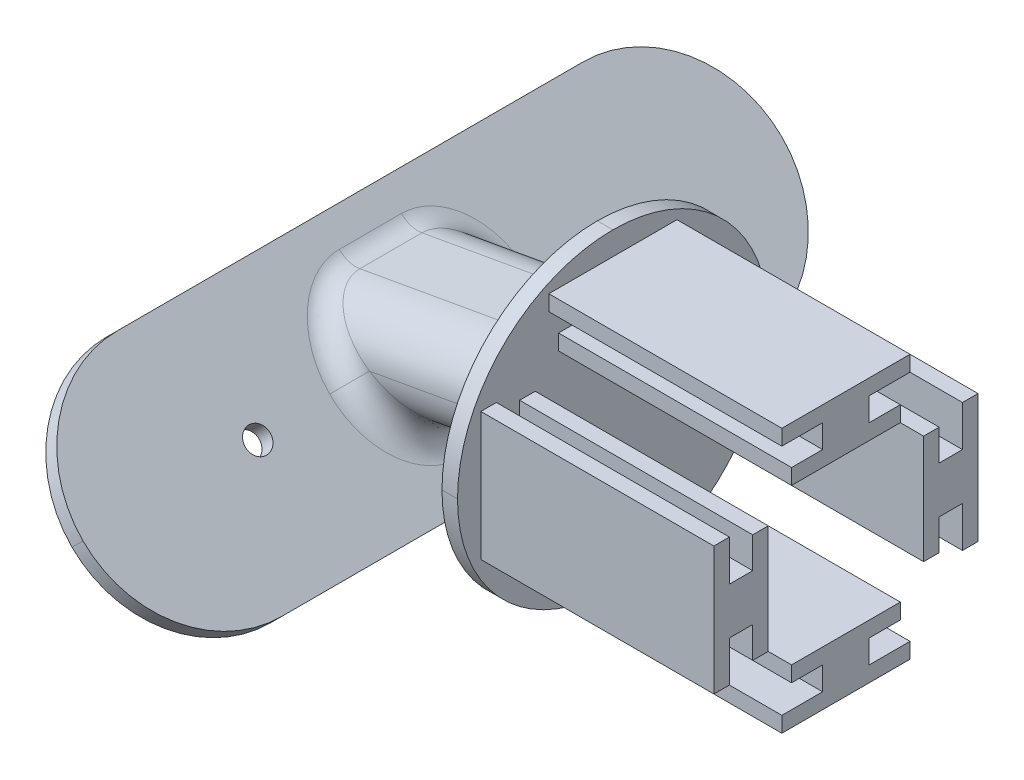
SolidWorks part; units mm, degrees
ref_plane "Front Plane" through (0, 0, 0) normal (0, 0, 1) x (1, 0, 0)
ref_plane "Top Plane" through (0, 0, 0) normal (0, 1, 0) x (1, 0, 0)
ref_plane "Right Plane" through (0, 0, 0) normal (1, 0, 0) x (0, 0, -1)
sketch "Sketch1" plane through (0, 0, 0) normal (0, 0, 1) x (1, 0, 0)
  line L0 (0, -20) -> (0, 20)
  line L1 (0, -20) -> (0, -25) construction
  line L2 (0, -25) -> (-10.6066, -14.3934) construction
  line L3 (-10.6066, -14.3934) -> (-31.8198, 6.8198)
  line L4 (-31.8198, 6.8198) -> (-33.234, 5.4056)
  line L5 (-33.234, 5.4056) -> (-12.0208, -15.8076)
  line L6 (-12.0208, -15.8076) -> (-10.6066, -14.3934)
  line L7 (0, 20) -> (2, 20)
  line L8 (2, 20) -> (2, -20)
  line L9 (0, -20) -> (2, -20)
  line L10 (-21.2132, -3.7868) -> (0, 0)
  line L11 (-28.1087, 3.1087) -> (0, 8.1265)
  line L12 (-20.5103, -7.7245) -> (-20.1654, -7.663)
  line L13 (-17.7654, -7.2346) -> (0, -4.0632)
  line L14 (-28.1087, 3.1087) -> (-21.2132, -3.7868)
  line L15 (-20.5103, -7.7245) -> (0.7029, -3.9378) construction
  line L16 (-21.2132, -3.7868) -> (-17.7654, -7.2346)
  line L17 (0, 8.1265) -> (0, 0)
  line L18 (0, -4.0632) -> (0, 0)
  point P4 (0, 0)
  dimension "D1" = 40
  dimension "D2" = 5
  dimension "D3" = 45
  dimension "D4" = 15
  dimension "D5" = 30
  dimension "D6" = 2
  dimension "D7" = 2
  dimension "D8" = 8
  dimension "D9" = 4
extrude "Boss-Extrude1" add sketch "Sketch1" along normal mid plane 90 contours L5 L6 L3 L4 region at (-21.9203, -4.4939, 0)
extrude "Boss-Extrude2" add sketch "Sketch1<3>" along normal mid plane 40 separate body contours L0 L7 L8 L9
sketch "Sketch1<3>" plane through (0, 0, 0) normal (0, 0, 1) x (1, 0, 0) same geometry as "Sketch1"
extrude "Boss-Extrude3" add sketch "Sketch1<4>" along normal mid plane 20 contours L11 L3 L10 L0 | L3 L13 L0 L10 region at (-9.7701, -3.7158, 0) region at (-12.4108, 2.0371, 0)
sketch "Sketch1<4>" plane through (0, 0, 0) normal (0, 0, 1) x (1, 0, 0) same geometry as "Sketch1"
sketch "Sketch2" plane through (2, 0, 0) normal (1, 0, 0) x (0, 0, -1)
  line L0 (0, 0) -> (0, 20) construction
  line L1 (-20, 20) -> (20, 20) construction
  line L2 (0, 0) -> (0, 15) construction
  line L3 (-15, -15) -> (15, -15) construction
  line L4 (-15, -15) -> (-15, 15) construction
  line L5 (-15, 15) -> (15, 15) construction
  line L6 (15, -15) -> (15, 15) construction
  line L7 (-15, -15) -> (15, 15) construction
  line L8 (-15, 15) -> (15, -15) construction
  line L9 (-8.25, 15) -> (8.25, 15)
  line L10 (-8.25, 15) -> (-8.25, 17)
  line L11 (-8.25, 17) -> (8.25, 17)
  line L12 (8.25, 17) -> (8.25, 15)
  line L13 (-7, 12) -> (7, 12)
  line L14 (-7, 12) -> (-7, 10)
  line L15 (-7, 10) -> (7, 10)
  line L16 (7, 10) -> (7, 12)
  line L17 (-3, 15) -> (-3, 12)
  line L18 (3, 15) -> (3, 12)
  line L19 (15, 8.25) -> (15, -8.25)
  line L20 (17, -8.25) -> (15, -8.25)
  line L21 (17, 8.25) -> (17, -8.25)
  line L22 (15, 8.25) -> (17, 8.25)
  line L23 (12, 7) -> (12, -7)
  line L24 (10, -7) -> (12, -7)
  line L25 (10, 7) -> (10, -7)
  line L26 (12, 7) -> (10, 7)
  line L27 (15, -3) -> (12, -3)
  line L28 (15, 3) -> (12, 3)
  line L29 (8.25, -15) -> (-8.25, -15)
  line L30 (-8.25, -17) -> (-8.25, -15)
  line L31 (8.25, -17) -> (-8.25, -17)
  line L32 (8.25, -15) -> (8.25, -17)
  line L33 (7, -12) -> (-7, -12)
  line L34 (-7, -10) -> (-7, -12)
  line L35 (7, -10) -> (-7, -10)
  line L36 (7, -12) -> (7, -10)
  line L37 (-3, -15) -> (-3, -12)
  line L38 (3, -15) -> (3, -12)
  line L39 (-15, -8.25) -> (-15, 8.25)
  line L40 (-17, 8.25) -> (-15, 8.25)
  line L41 (-17, -8.25) -> (-17, 8.25)
  line L42 (-15, -8.25) -> (-17, -8.25)
  line L43 (-12, -7) -> (-12, 7)
  line L44 (-10, 7) -> (-12, 7)
  line L45 (-10, -7) -> (-10, 7)
  line L46 (-12, -7) -> (-10, -7)
  line L47 (-15, 3) -> (-12, 3)
  line L48 (-15, -3) -> (-12, -3)
  point P5 (0, 0)
  point P15 (0, 15)
  point P20 (0, 12)
  point P65 (0, 0)
  dimension "D1" = 30
  dimension "D2" = 30
  dimension "D3" = 16.5
  dimension "D4" = 2
  dimension "D5" = 3
  dimension "D6" = 14
  dimension "D7" = 2
  dimension "D8" = 3
  dimension "D9" = 4
extrude "Boss-Extrude4" add sketch "Sketch2" along normal blind 30 contours L23 L26 L25 L24 | L19 L28 L23 L27 | L18 L9 L17 L13 | L12 L11 L10 L9 | L43 L46 L45 L44 | L39 L48 L43 L47 | L42 L39 L40 L41 | L33 L36 L35 L34 | L29 L38 L33 L37 | L32 L29 L30 L31 | L21 L20 L19 L22 | L13 L16 L15 L14 region at (2, 16, 0) region at (2, 13.5, 0) region at (2, 0, -13.5) region at (2, 0, -11) region at (2, -16, 0) region at (2, -13.5, 0) region at (2, -11, 0) region at (2, 0, 16) region at (2, 0, 13.5) region at (2, 0, 11)
sketch "Sketch3" plane through (-13.9142, -13.9142, 0) normal (-0.7071, -0.7071, 0) x (0.7071, -0.7071, 0)
  line L0 (2.6777, 0) -> (-27.3223, 0) construction
  line L1 (2.6777, 45) -> (2.6777, -45) construction
  line L2 (-27.3223, 45) -> (-27.3223, -45) construction
  line L3 (-12.3223, 0) -> (-12.3223, 22.5) construction
  circle A0 centre (-12.3223, 22.5) radius 1.6
  circle A1 centre (-12.3223, -22.5) radius 1.6
  dimension "D2" = 3.2
  dimension "D1" = 22.5
extrude "Cut-Extrude1" cut sketch "Sketch3" against normal through all
fillet "Fillet1" radius 20 4 edges at (1, -20, -20) (1, -20, 20) (1, 20, -20) (1, 20, 20)
fillet "Fillet2" radius 15 4 edges at (-11.3137, -15.1005, -45) (-32.5269, 6.1127, -45) (-11.3137, -15.1005, 45) (-32.5269, 6.1127, 45)
fillet "Fillet3" radius 6 4 edges at (-8.8827, -5.6489, -10) (-8.8827, -5.6489, 10) (-14.0544, 5.6176, 10) (-14.0544, 5.6176, -10)
fillet "Fillet4" radius 5 6 edges at (0, 6.3413, 8.2426) (0, -2.2781, 8.2426) (0, -4.0632, 0) (0, -2.2781, -8.2426) (0, 6.3413, -8.2426) (0, 8.1265, 0)
fillet "Fillet5" radius 3 6 edges at (-19.2802, -5.7198, 8.2426) (-17.7654, -7.2346, 0) (-19.2802, -5.7198, -8.2426) (-26.594, 1.594, -8.2426) (-28.1087, 3.1087, 0) (-26.594, 1.594, 8.2426)
